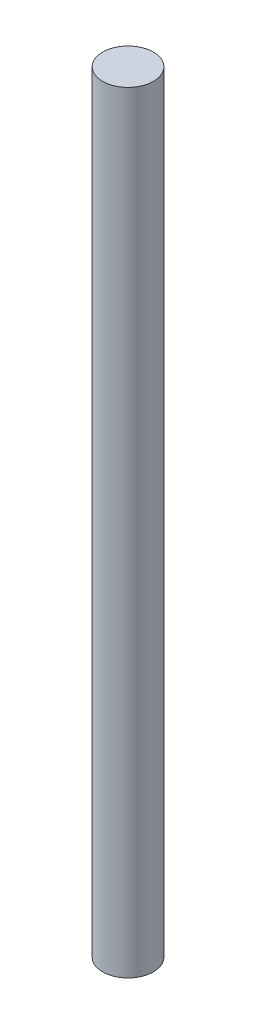
SolidWorks part; units mm, degrees
ref_plane "Front Plane" through (0, 0, 0) normal (0, 0, 1) x (1, 0, 0)
ref_plane "Top Plane" through (0, 0, 0) normal (0, 1, 0) x (1, 0, 0)
ref_plane "Right Plane" through (0, 0, 0) normal (1, 0, 0) x (0, 0, -1)
sketch "Sketch1" plane through (0, 0, 0) normal (0, 1, 0) x (1, 0, 0)
  circle A0 centre (0, 0) radius 15.875
  dimension "D1" = 31.75
extrude "Boss-Extrude1" add sketch "Sketch1" along normal blind 482.6 contours A0
sketch "Sketch2" plane through (0, 0, 0) normal (0, -1, 0) x (1, 0, 0)
  circle A0 centre (0, 0) radius 11.43 construction
  circle A1 centre (0, 11.43) radius 2.1971
  circle A2 centre (11.43, 0) radius 2.1971
  circle A3 centre (0, -11.43) radius 2.1971
  circle A4 centre (-11.43, 0) radius 2.1971
  point P5 (0, 0)
  point P6 (0, 0)
  point P7 (0, -10.16)
  dimension "D1" = 22.86
  dimension "D2" = 4.3942
  dimension "D3" = 4
extrude "Cut-Extrude1" cut sketch "Sketch2" against normal blind 76.2
